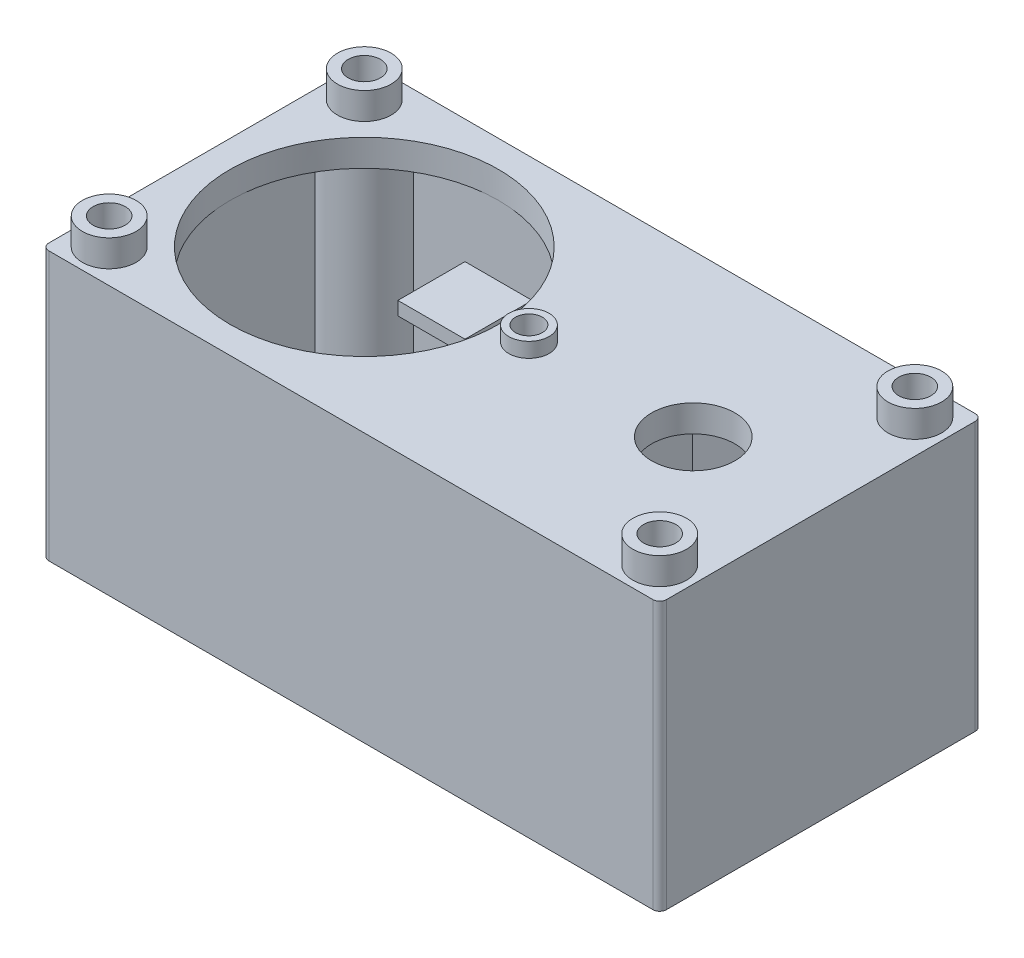
SolidWorks part; units mm, degrees
ref_plane "Front Plane" through (0, 0, 0) normal (0, 0, 1) x (1, 0, 0)
ref_plane "Top Plane" through (0, 0, 0) normal (0, 1, 0) x (1, 0, 0)
ref_plane "Right Plane" through (0, 0, 0) normal (1, 0, 0) x (0, 0, -1)
sketch "Sketch1" plane through (0, 0, 0) normal (0, 1, 0) x (1, 0, 0)
  line L0 (0, 0) -> (0, -6) construction
  line L1 (-11.5, 6) -> (11.5, 6)
  line L2 (-11.5, 6) -> (-11.5, -6)
  line L3 (-11.5, -6) -> (11.5, -6)
  line L4 (11.5, 6) -> (11.5, -6)
  line L5 (-11.5, 6) -> (11.5, -6) construction
  line L6 (-11.5, -6) -> (11.5, 6) construction
  circle A0 centre (-10.25, 4.75) radius 0.6
  circle A1 centre (-10.25, -4.75) radius 0.6
  circle A2 centre (10.25, -4.75) radius 0.6
  circle A3 centre (10.25, 4.75) radius 0.6
  point P0 (0, 0)
  dimension "D4" = 1.2
  dimension "D1" = 12
  dimension "D2" = 23
  dimension "D3" = 1.25
  dimension "D5" = 1.25
  dimension "D6" = 1.25
extrude "Boss-Extrude1" add sketch "Sketch1" along normal blind 10
shell "Shell1" thickness 1 removed face at (0, 0, 0)
extrude "Extrude-Thin1" add sketch "Sketch1<4>" along normal blind 1 from offset 10 thin contours A3 | A2 | A1 | A0 thin type one direction wall 0.4
sketch "Sketch1<4>" plane through (0, 0, 0) normal (0, 1, 0) x (1, 0, 0) same geometry as "Sketch1"
sketch "Sketch2" plane through (0, 10, 0) normal (0, 1, 0) x (1, 0, 0)
  line L0 (11.5, 6) -> (11.5, -6) construction
  line L1 (-11.5, 6) -> (-11.5, -6) construction
  circle A0 centre (-5.5, 0) radius 5
  circle A1 centre (6.75, 0) radius 1.55
  circle A2 centre (0.63, 0) radius 0.75
  dimension "D1" = 3.1
  dimension "D3" = 10
  dimension "D5" = 1.5
  dimension "D2" = 4.75
  dimension "D4" = 6
  dimension "D6" = 6.13
extrude "Cut-Extrude1" cut sketch "Sketch2" against normal up to next contours A0 | A1 region at (-5.5, 10, 0) region at (6.75, 10, 0)
extrude "Extrude-Thin2" add sketch "Sketch2<4>" along normal blind 0.55 thin contours A2 thin type one direction reverse wall 0.25
sketch "Sketch2<4>" plane through (0, 10, 0) normal (0, 1, 0) x (1, 0, 0) same geometry as "Sketch2"
sketch "Sketch3" plane through (0, 10, 0) normal (0, 1, 0) x (1, 0, 0)
  circle A1 centre (0.63, 0) radius 0.5
  circle A2 centre (0.63, 0) radius 0.5
  dimension "D1" = 0
extrude "Cut-Extrude2" cut sketch "Sketch3" against normal blind 0.3
sketch "Sketch4" plane through (0, 9, 0) normal (0, -1, 0) x (1, 0, 0)
  line L0 (4.975, 5) -> (3.35, 3.375)
  line L1 (-5.5, 5) -> (8.6697, 5) construction
  line L2 (3.35, 3.375) -> (3.35, -3.375)
  line L3 (3.35, -3.375) -> (4.975, -5)
  line L4 (8.6697, -5) -> (-5.5, -5) construction
  line L5 (10.5, 3.1697) -> (10.5, -3.1697) construction
  dimension "D1" = 7.15
  dimension "D2" = 135
  dimension "D3" = 135
  dimension "D4" = 6.75
extrude "Extrude-Thin3" add sketch "Sketch4" along normal blind 5 thin thin type one direction wall 0.5
sketch "Sketch7" plane through (0, 10, 0) normal (0, 1, 0) x (1, 0, 0)
  line L0 (-5.5, 5) -> (-8.6697, 5) construction
  line L1 (-6.75, 5) -> (-4.25, 5)
  line L2 (-6.75, 5) -> (-6.75, 2.5)
  line L3 (-6.75, 2.5) -> (-4.25, 2.5)
  line L4 (-4.25, 5) -> (-4.25, 2.5)
  line L5 (-5.5, 0) -> (-7.8839, 0) construction
  line L6 (-4.25, -5) -> (-4.25, -2.5)
  line L7 (-6.75, -2.5) -> (-4.25, -2.5)
  line L8 (-6.75, -5) -> (-6.75, -2.5)
  line L9 (-6.75, -5) -> (-4.25, -5)
  point P6 (-5.5, 2.5)
  dimension "D1" = 2.5
extrude "Boss-Extrude3" add sketch "Sketch7" against normal blind 0.5 from offset 3.6 offset against normal yes
fillet "Fillet1" radius 0.25 4 edges at (11.5, 5, 6) (11.5, 5, -6) (-11.5, 5, -6) (-11.5, 5, 6)
